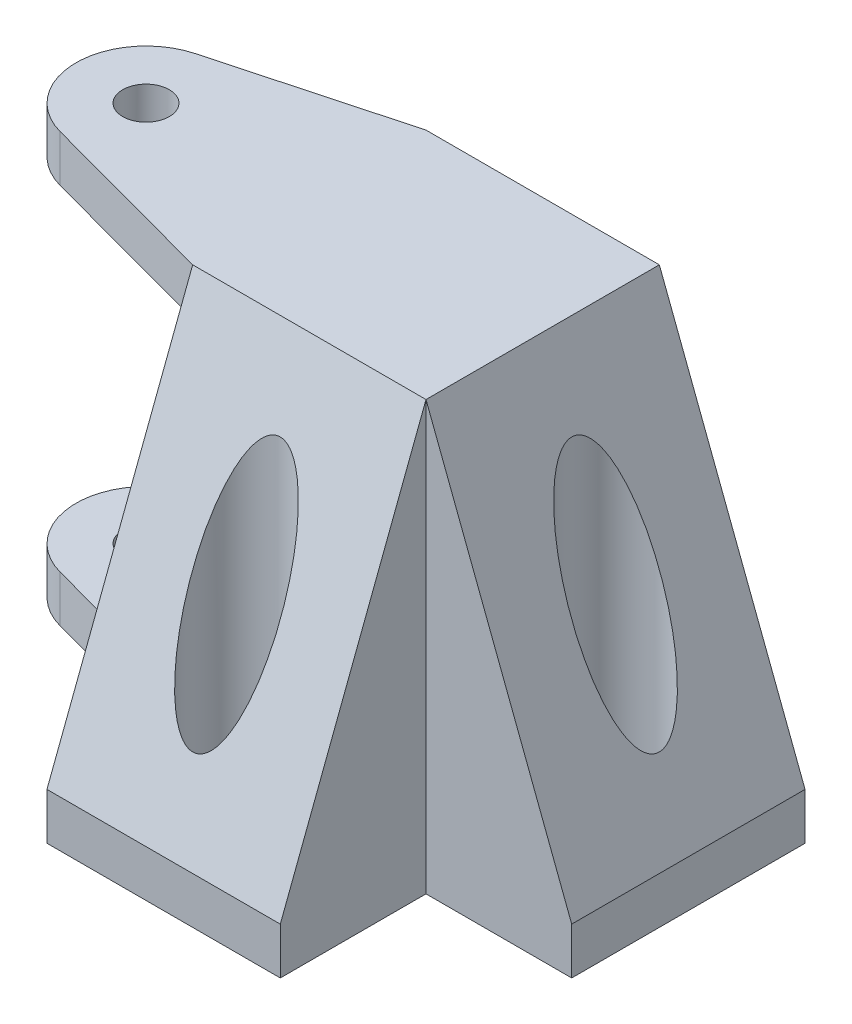
SolidWorks part; units mm, degrees
ref_plane "Front Plane" through (0, 0, 0) normal (0, 0, 1) x (1, 0, 0)
ref_plane "Top Plane" through (0, 0, 0) normal (0, 1, 0) x (1, 0, 0)
ref_plane "Right Plane" through (0, 0, 0) normal (1, 0, 0) x (0, 0, -1)
sketch "Sketch2" plane through (0, 0, 0) normal (0, 0, 1) x (1, 0, 0)
  line L0 (0, 0) -> (-40, 0)
  line L1 (0, 73.3918) -> (24.9782, 8)
  line L2 (24.9782, 8) -> (24.9782, 0)
  line L3 (0, 0) -> (24.9782, 0)
  line L4 (-40, 0) -> (-40, 73.3918)
  line L5 (-40, 73.3918) -> (0, 73.3918)
  dimension "D1" = 40
  dimension "D2" = 8
  dimension "D3" = 70
extrude "Boss-Extrude1" add sketch "Sketch2" along normal blind 40
sketch "Sketch3" plane through (0, 73.3918, 0) normal (0, 1, 0) x (1, 0, 0)
  line L0 (-40, -40) -> (-40, 0) construction
  line L1 (-40, -40) -> (-71.1316, -31.5842)
  line L2 (-40, 0) -> (-71.1316, -8.4158)
  line L3 (-40, 0) -> (-40, -40)
  arc A0 (-71.1316, -31.5842) -> (-71.1316, -8.4158) centre (-68, -20) cw
  point P3 (-80, -20)
  dimension "D2" = 20
  dimension "D1" = 40
extrude "Boss-Extrude2" add sketch "Sketch3" against normal up to vertex (73.3918 mm away) contours L1 A0 L2 L3 up to point (-40, 0, 40)
sketch "Sketch4" plane through (0, 0, 0) normal (0, 0, 1) x (1, 0, 0)
  line L0 (-40, 73.3918) -> (-40, 65.3918) construction
  line L1 (-40, 73.3918) -> (-40, 0) construction
  line L2 (-40, 73.3918) -> (-71.1316, 73.3918) construction
  line L3 (-40, 0) -> (-40, 8) construction
  line L4 (22, 0) -> (-22, 0) construction
  line L5 (-40, 8) -> (-40, 65.3918)
  line L6 (-40, 65.3918) -> (-80, 65.3918)
  line L7 (-80, 73.3918) -> (-80, 0) construction
  line L8 (-80, 65.3918) -> (-80, 8)
  line L9 (-80, 8) -> (-40, 8)
  dimension "D1" = 8
  dimension "D2" = 8
extrude "Cut-Extrude1" cut sketch "Sketch4" along normal blind 73
sketch "Sketch6" plane through (0, 0, 0) normal (1, 0, 0) x (0, 0, -1)
  line L0 (-40, 73.3918) -> (-64.9782, 8)
  line L1 (-64.9782, 8) -> (-64.9782, 0)
  line L2 (22, 0) -> (-22, 0) construction
  line L3 (-64.9782, 0) -> (-40, 0)
  line L4 (-40, 0) -> (-40, 8) construction
  line L5 (-40, 73.3918) -> (-40, 0)
  dimension "D1" = 8
  dimension "D2" = 70
extrude "Boss-Extrude4" add sketch "Sketch6" against normal blind 40
sketch "Sketch8" plane through (0, 73.3918, 0) normal (0, 1, 0) x (1, 0, 0)
  circle A0 centre (12.4891, -20) radius 4
  circle A1 centre (-20, -52.4891) radius 4
  circle A2 centre (-68, -20) radius 4
  dimension "D1" = 8
  dimension "D2" = 8
  dimension "D3" = 8
extrude "Cut-Extrude2" cut sketch "Sketch8" against normal through all contours A0 | A1 | A2
ref_plane "Plane1" through (0, 5, 0) normal (0, 1, 0) x (1, 0, 0)
sketch "Sketch10" plane through (0, 5, 0) normal (0, 1, 0) x (1, 0, 0)
  circle A0 centre (12.4891, -20) radius 7.5
  circle A1 centre (-20, -52.4891) radius 7.5
  dimension "D1" = 15
  dimension "D2" = 15
extrude "Cut-Extrude3" cut sketch "Sketch10" along normal through all
